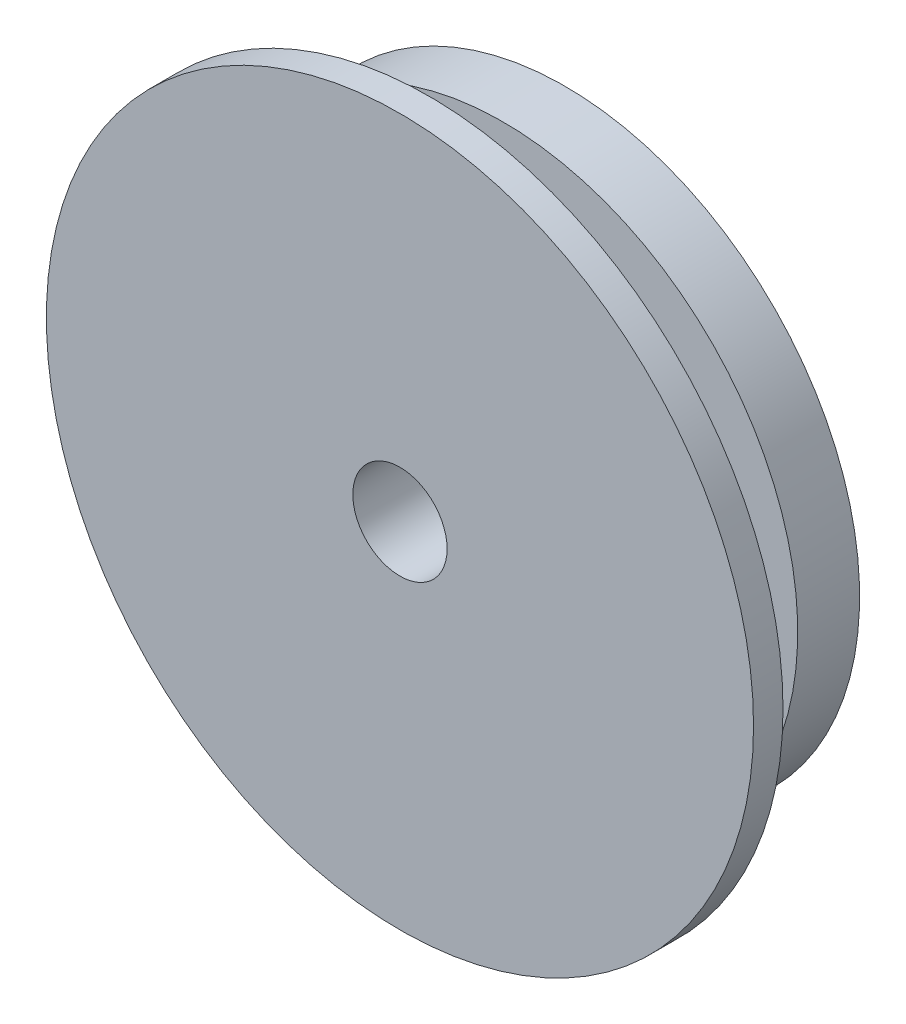
SolidWorks part; units mm, degrees
material "Resina de melamina"
ref_plane "Alzado" through (0, 0, 0) normal (0, 0, 1) x (1, 0, 0)
ref_plane "Planta" through (0, 0, 0) normal (0, 1, 0) x (1, 0, 0)
ref_plane "Vista lateral" through (0, 0, 0) normal (1, 0, 0) x (0, 0, -1)
sketch "Croquis1" plane through (0, 0, 0) normal (0, 0, 1) x (1, 0, 0)
  circle A0 centre (0, 0) radius 11
  circle A1 centre (0, 0) radius 25
  dimension "D1" = 50
  dimension "D2" = 22
extrude "Saliente-Extruir1" add sketch "Croquis1" along normal blind 15.5
ref_plane "Plano1" through (0, 0, 6) normal (0, 0, -1) x (-1, 0, 0)
sketch "Croquis3" plane through (0, 0, 6) normal (0, 0, -1) x (-1, 0, 0)
  circle A0 centre (0, 0) radius 11
  circle A1 centre (0, 0) radius 9.5
  dimension "D1" = 19
extrude "Saliente-Extruir2" add sketch "Croquis3" against normal through all
sketch "Croquis4" plane through (0, 0, 15.5) normal (0, 0, 1) x (1, 0, 0)
  circle A0 centre (0, 0) radius 11
  circle A1 centre (0, 0) radius 4
  dimension "D1" = 8
extrude "Saliente-Extruir3" add sketch "Croquis4" against normal blind 2
sketch "Croquis5" plane through (0, 0, 15.5) normal (0, 0, 1) x (1, 0, 0)
  circle A0 centre (0, 0) radius 25
  circle A1 centre (0, 0) radius 30
  dimension "D1" = 60
extrude "Saliente-Extruir4" add sketch "Croquis5" against normal blind 2.5
ref_plane "Plano2" through (0, 0, 10.75) normal (0, 0, -1) x (-1, 0, 0)
sketch "Croquis6" plane through (0, 0, 10.75) normal (0, 0, -1) x (-1, 0, 0)
  circle A1 centre (0, 0) radius 25
  circle A2 centre (0, 0) radius 19
  dimension "D1" = 38
extrude "Cortar-Extruir1" cut sketch "Croquis6" along normal blind 4
sketch "Croquis7" plane through (0, 0, 0) normal (0, 0, -1) x (-1, 0, 0)
  circle A0 centre (0, 0) radius 11
  circle A1 centre (0, 0) radius 4
extrude "Saliente-Extruir5" add sketch "Croquis7" against normal through all
sketch "Croquis8" plane through (0, 0, 0) normal (0, 0, -1) x (-1, 0, 0)
  circle A0 centre (0, 0) radius 6.1
  circle A1 centre (0, 0) radius 4
  dimension "D1" = 12.2
extrude "Saliente-Extruir6" add sketch "Croquis8" along normal blind 1.5
sketch "Croquis11" plane through (0, 0, 0) normal (0, 0, -1) x (-1, 0, 0)
  circle A0 centre (0, 0) radius 15
  circle A1 centre (0, 0) radius 25
  dimension "D1" = 30
extrude "Cortar-Extruir2" cut sketch "Croquis11" against normal blind 1.5
